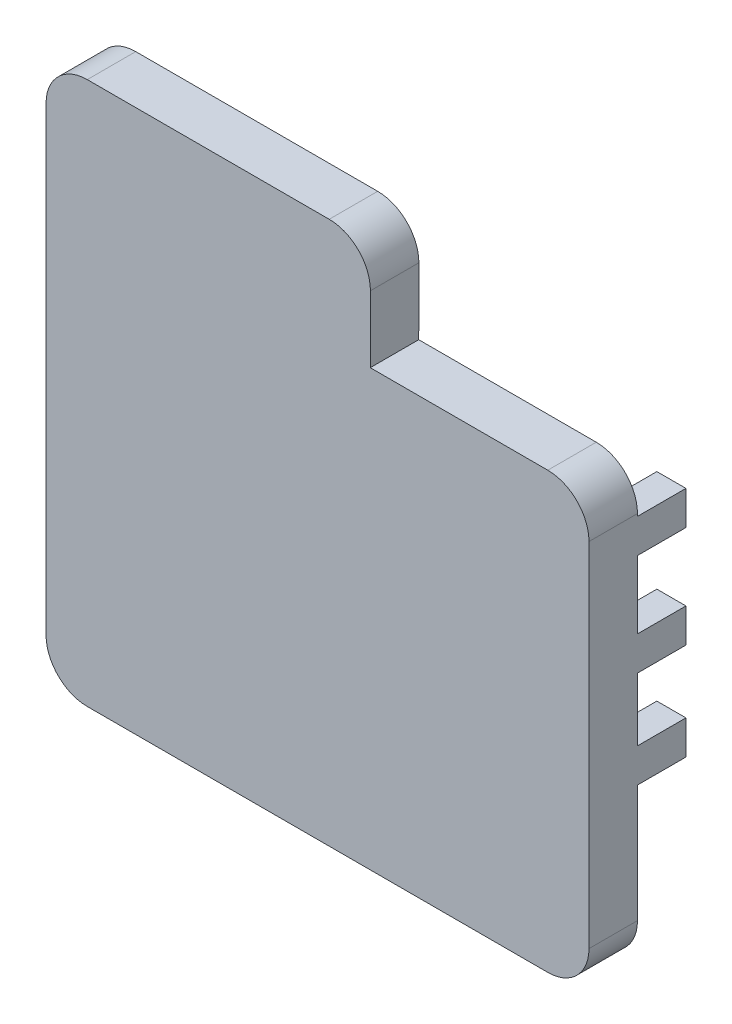
SolidWorks part; units mm, degrees
ref_plane "Front Plane" through (0, 0, 0) normal (0, 0, 1) x (1, 0, 0)
ref_plane "Top Plane" through (0, 0, 0) normal (0, 1, 0) x (1, 0, 0)
ref_plane "Right Plane" through (0, 0, 0) normal (1, 0, 0) x (0, 0, -1)
sketch "Sketch1" plane through (0, 0, 0) normal (0, 0, 1) x (1, 0, 0)
  line L52 (82.4772, 143.7329) -> (82.4772, 136.7329)
  line L53 (82.4772, 136.7329) -> (88.4772, 136.7329)
  line L54 (88.4772, 136.7329) -> (88.4772, 143.7329)
  line L55 (88.4772, 143.7329) -> (82.4772, 143.7329)
  line L56 (88.4772, 136.7329) -> (82.4772, 136.7329)
  line L57 (82.4772, 136.7329) -> (82.4772, 122.7329)
  line L58 (82.4772, 122.7329) -> (88.4772, 122.7329)
  line L59 (88.4772, 122.7329) -> (88.4772, 136.7329)
  line L60 (82.4772, 122.7329) -> (82.4772, 115.7329)
  line L61 (82.4772, 115.7329) -> (88.4772, 115.7329)
  line L62 (88.4772, 115.7329) -> (88.4772, 122.7329)
  line L63 (88.4772, 122.7329) -> (82.4772, 122.7329)
  line L64 (88.4772, 115.7329) -> (82.4772, 115.7329)
  line L65 (82.4772, 115.7329) -> (82.4772, 102.7329)
  line L66 (82.4772, 102.7329) -> (88.4772, 102.7329)
  line L67 (88.4772, 102.7329) -> (88.4772, 115.7329)
  line L68 (82.4772, 102.7329) -> (82.4772, 95.7329)
  line L69 (82.4772, 95.7329) -> (88.4772, 95.7329)
  line L70 (88.4772, 95.7329) -> (88.4772, 102.7329)
  line L71 (88.4772, 102.7329) -> (82.4772, 102.7329)
  line L72 (-17.5228, 97.5129) -> (-23.5228, 97.5129)
  line L73 (-23.5228, 97.5129) -> (-23.5228, 71.5129)
  line L74 (-15.0228, 63.0129) -> (79.9772, 63.0129)
  line L75 (88.4772, 71.5129) -> (88.4772, 95.7329)
  line L76 (88.4772, 95.7329) -> (82.4772, 95.7329)
  line L77 (82.4772, 95.7329) -> (82.4772, 71.5129)
  line L78 (79.9772, 69.0129) -> (-15.0228, 69.0129)
  line L79 (-17.5228, 71.5129) -> (-17.5228, 97.5129)
  line L80 (-23.5228, 104.5129) -> (-23.5228, 97.5129)
  line L81 (-23.5228, 97.5129) -> (-17.5228, 97.5129)
  line L82 (-17.5228, 97.5129) -> (-17.5228, 104.5129)
  line L83 (-17.5228, 104.5129) -> (-23.5228, 104.5129)
  line L84 (-23.5228, 104.5129) -> (-17.5228, 104.5129)
  line L85 (-17.5228, 104.5129) -> (-17.5228, 134.0129)
  line L86 (-17.5228, 134.0129) -> (-23.5228, 134.0129)
  line L87 (-23.5228, 134.0129) -> (-23.5228, 104.5129)
  line L88 (-23.5228, 141.0129) -> (-23.5228, 134.0129)
  line L89 (-23.5228, 134.0129) -> (-17.5228, 134.0129)
  line L90 (-17.5228, 134.0129) -> (-17.5228, 141.0129)
  line L91 (-17.5228, 141.0129) -> (-23.5228, 141.0129)
  line L92 (-23.5228, 141.0129) -> (-17.5228, 141.0129)
  line L93 (-17.5228, 141.0129) -> (-17.5228, 166.5129)
  line L94 (-15.0228, 169.0129) -> (34.8872, 169.0129)
  line L95 (37.3872, 166.5071) -> (37.3472, 149.2729)
  line L96 (39.8872, 146.7329) -> (79.9772, 146.7329)
  line L97 (82.4772, 144.2329) -> (82.4772, 143.7329)
  line L98 (82.4772, 143.7329) -> (88.4772, 143.7329)
  line L99 (88.4772, 143.7329) -> (88.4772, 144.2329)
  line L100 (79.9772, 152.7329) -> (43.3553, 152.7329)
  line L101 (43.3553, 152.7329) -> (43.3872, 166.4932)
  line L102 (34.8872, 175.0129) -> (-15.0228, 175.0129)
  line L103 (-23.5228, 166.5129) -> (-23.5228, 141.0129)
  arc A11 (-23.5228, 71.5129) -> (-15.0228, 63.0129) centre (-15.0228, 71.5129) ccw
  arc A12 (79.9772, 63.0129) -> (88.4772, 71.5129) centre (79.9772, 71.5129) ccw
  arc A13 (79.9772, 69.0129) -> (82.4772, 71.5129) centre (79.9772, 71.5129) ccw
  arc A14 (-17.5228, 71.5129) -> (-15.0228, 69.0129) centre (-15.0228, 71.5129) ccw
  arc A15 (-15.0228, 169.0129) -> (-17.5228, 166.5129) centre (-15.0228, 166.5129) ccw
  arc A16 (37.3872, 166.5071) -> (34.8872, 169.0129) centre (34.8872, 166.5129) ccw
  arc A17 (37.3472, 149.2729) -> (39.8872, 146.7329) centre (39.8872, 149.2729) ccw
  arc A18 (82.4772, 144.2329) -> (79.9772, 146.7329) centre (79.9772, 144.2329) ccw
  arc A19 (88.4772, 144.2329) -> (79.9772, 152.7329) centre (79.9772, 144.2329) ccw
  arc A20 (43.3872, 166.4932) -> (34.8872, 175.0129) centre (34.8872, 166.5129) ccw
  arc A21 (-15.0228, 175.0129) -> (-23.5228, 166.5129) centre (-15.0228, 166.5129) ccw
extrude "Boss-Extrude1" add sketch "Sketch1" along normal blind 10 contours L102 A21 L103 L91 L93 A15 L94 A16 L95 A17 L96 A18 L97 L55 L99 A19 L100 L101 A20 | L90 L91 L88 L86 | L86 L87 L83 L85 | L82 L83 L80 L72 | A14 L79 L72 L73 A11 L74 A12 L75 L69 L77 A13 L78 | L97 A18 L96 A17 L95 A16 L94 A15 L93 L90 L85 L82 L79 A14 L78 A13 L77 L68 L65 L60 L57 L52 | L54 L55 L52 L53 | L58 L59 L53 L57 | L61 L62 L58 L60 | L66 L67 L61 L65 | L69 L70 L66 L68 region at (85.4772, 140.2329, 0) region at (83.6477, 143.9829, 0) region at (29.409, 114.6688, 0) region at (85.4772, 129.7329, 0) region at (85.4772, 119.2329, 0) region at (85.4772, 109.2329, 0) region at (85.4772, 99.2329, 0) region at (85.4772, 94.561, 0) region at (-20.5228, 137.5129, 0) region at (-20.5228, 101.0129, 0) region at (-20.5228, 119.2629, 0)
extrude "Boss-Extrude2" add sketch "Sketch1<4>" against normal blind 10 contours L54 L55 L52 L53 | L61 L62 L58 L60 | L69 L70 L66 L68 | L82 L83 L80 L72 | L90 L91 L88 L86 region at (85.4772, 140.2329, 0) region at (85.4772, 119.2329, 0) region at (85.4772, 99.2329, 0) region at (-20.5228, 137.5129, 0) region at (-20.5228, 101.0129, 0)
sketch "Sketch1<4>" plane through (0, 0, 0) normal (0, 0, 1) x (1, 0, 0) same geometry as "Sketch1"
